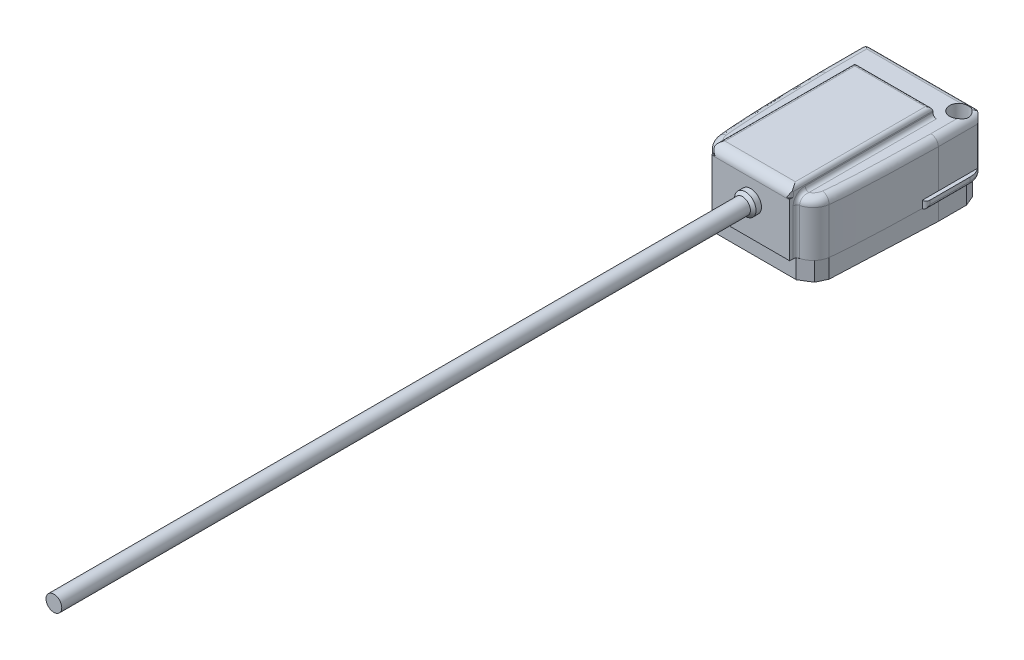
SolidWorks part; units mm, degrees
ref_plane "Front Plane" through (0, 0, 0) normal (0, 0, 1) x (1, 0, 0)
ref_plane "Top Plane" through (0, 0, 0) normal (0, 1, 0) x (1, 0, 0)
ref_plane "Right Plane" through (0, 0, 0) normal (1, 0, 0) x (0, 0, -1)
sketch "Sketch1" plane through (0, 0, 0) normal (0, 0, 1) x (1, 0, 0)
  circle A0 centre (0, 0) radius 4.2
  dimension "D1" = 8.4
extrude "Extrude1" add sketch "Sketch1" along normal blind 366.8
sketch "Sketch2" plane through (0, 0, 0) normal (0, 0, -1) x (-1, 0, 0)
  circle A0 centre (0, 0) radius 5.7
  dimension "D1" = 11.4
extrude "Extrude2" add sketch "Sketch2" along normal blind 4.4
chamfer "Chamfer1" distance 1.5 angle 45 1 edges at (-5.7, 0, 0)
sketch "Sketch3" plane through (0, 0, -4.4) normal (0, 0, -1) x (-1, 0, 0)
  line L1 (-34.1, 15.75) -> (34.1, 15.75)
  line L2 (-34.1, 15.75) -> (-34.1, -17.25)
  line L3 (-34.1, -17.25) -> (34.1, -17.25)
  line L4 (34.1, 15.75) -> (34.1, -17.25)
  circle A0 centre (0, 0) radius 5.7 construction
  dimension "D4" = 17.25
  dimension "D1" = 33
  dimension "D2" = 68.2
  dimension "D3" = 34.1
extrude "Extrude3" add sketch "Sketch3" along normal blind 92.8
sketch "Sketch4" plane through (-34.1, 0, 0) normal (-1, 0, 0) x (0, 0, 1)
  line L0 (-97.2, 15.75) -> (-4.4, 15.75) construction
  line L1 (-80.6, 41.999) -> (-107.8441, 41.999)
  line L2 (-80.6, 41.999) -> (-80.6, 11.15)
  line L3 (-80.6, 11.15) -> (-107.8441, 11.15)
  line L4 (-107.8441, 41.999) -> (-107.8441, 11.15)
  line L5 (-97.2, -17.25) -> (-97.2, 15.75) construction
  dimension "D1" = 4.6
  dimension "D2" = 16.6
extrude "Extrude4" cut sketch "Sketch4" against normal up to next
sketch "Sketch5" plane through (0, 0, -80.6) normal (0, 0, -1) x (-1, 0, 0)
  line L1 (20.75, 22.4945) -> (34.1, 22.4945)
  line L2 (20.75, 22.4945) -> (20.75, 11.15)
  line L3 (20.75, 11.15) -> (34.1, 11.15)
  line L4 (34.1, 22.4945) -> (34.1, 11.15)
  line L5 (-20.75, 22.4945) -> (-34.1, 22.4945)
  line L6 (-20.75, 22.4945) -> (-20.75, 11.15)
  line L7 (-20.75, 11.15) -> (-34.1, 11.15)
  line L8 (-34.1, 22.4945) -> (-34.1, 11.15)
  dimension "D1" = 41.5
  dimension "D2" = 13.35
  dimension "D3" = 13.35
extrude "Extrude5" cut sketch "Sketch5" against normal through all
sketch "Sketch6" plane through (0, 0, -97.2) normal (0, 0, -1) x (-1, 0, 0)
  line L0 (-34.1, -17.25) -> (34.1, -17.25) construction
  line L1 (32.1, 16.9028) -> (44.4445, 16.9028)
  line L2 (32.1, 16.9028) -> (32.1, -13.25)
  line L3 (32.1, -13.25) -> (44.4445, -13.25)
  line L4 (44.4445, 16.9028) -> (44.4445, -13.25)
  line L5 (-32.1, 22.2797) -> (-36.4812, 22.2797)
  line L6 (-32.1, 22.2797) -> (-32.1, -13.25)
  line L7 (-32.1, -13.25) -> (-36.4812, -13.25)
  line L8 (-36.4812, 22.2797) -> (-36.4812, -13.25)
  line L9 (-34.1, 11.15) -> (-34.1, -17.25) construction
  line L10 (34.1, -17.25) -> (34.1, 11.15) construction
  dimension "D1" = 4
  dimension "D2" = 4
  dimension "D3" = 2
  dimension "D4" = 2
extrude "Extrude6" cut sketch "Sketch6" against normal through all
sketch "Sketch7" plane through (0, -13.25, 0) normal (0, 1, 0) x (1, 0, 0)
  line L0 (32.1, 4.4) -> (32.1, 97.2) construction
  line L1 (58.6671, 1.609) -> (32.1, 1.609)
  line L2 (58.6671, 1.609) -> (58.6671, 63.7)
  line L3 (58.6671, 63.7) -> (32.1, 63.7)
  line L4 (32.1, 1.609) -> (32.1, 63.7)
  line L5 (-32.1, 4.4) -> (-32.1, 97.2) construction
  line L6 (-32.1, 63.7) -> (-46.2188, 63.7)
  line L7 (-32.1, 63.7) -> (-32.1, -25.5687)
  line L8 (-32.1, -25.5687) -> (-46.2188, -25.5687)
  line L9 (-46.2188, 63.7) -> (-46.2188, -25.5687)
  line L10 (-32.1, 97.2) -> (-34.1, 97.2) construction
  line L11 (34.1, 97.2) -> (32.1, 97.2) construction
  dimension "D1" = 33.5
  dimension "D2" = 33.5
extrude "Extrude7" cut sketch "Sketch7" against normal through all
fillet "Fillet2" radius 3 1 edges at (0, 11.15, -97.2)
fillet "Fillet3" radius 10 2 edges at (34.1, -15.25, -97.2) (-34.1, -15.25, -97.2)
fillet "Fillet20" radius 2 5 edges at (20.75, 13.45, -4.4) (20.75, 15.75, -42.5) (0, 15.75, -80.6) (-20.75, 15.75, -42.5) (-20.75, 13.45, -4.4)
fillet "Fillet7" radius 2 7 edges at (31.1711, -17.25, -94.2711) (-31.1711, -17.25, -94.2711) (-34.1, -15.25, -63.7) (34.1, -15.25, -63.7) (34.1, -17.25, -75.45) (0, -17.25, -97.2) (-34.1, -17.25, -75.45)
sketch "Sketch10" plane through (0, 15.75, 0) normal (0, 1, 0) x (1, 0, 0)
  line L0 (32.1, 4.4) -> (32.1, 93.2) construction
  line L2 (48.4518, 2.5489) -> (32.1, 35.6175)
  line L3 (-24.1, 97.2) -> (24.1, 97.2) construction
  line L4 (32.1, 35.6175) -> (32.1, 72.2)
  line L5 (48.4518, 2.5489) -> (34.583, 0.9729)
  line L6 (34.583, 0.9729) -> (26.1, 4.4)
  line L7 (-26.1, 4.4) -> (-37.3372, -2.8116)
  line L8 (-37.3372, -2.8116) -> (-32.1, 42.0539)
  line L9 (-32.1, 93.2) -> (-32.1, 4.4) construction
  line L10 (-32.1, 42.0539) -> (-32.1, 72.2)
  line L11 (18.75, 4.4) -> (18.75, 78.6) construction
  line L12 (-18.75, 4.4) -> (18.75, 4.4) construction
  spline S0 degree 3 poles (32.1, 72.2) (31.9027, 62.1371) (31.5864, 46.0005) (30.5599, 25.0431) (29.4595, 12.1255) (26.788, 5.9822) (26.1, 4.4) knots 0 0 0 0 0.440913 0.707031 0.924545 1 1 1 1
  spline S1 degree 3 poles (-32.1, 72.2) (-31.9027, 62.1371) (-31.5864, 46.0005) (-30.5599, 25.0431) (-29.4595, 12.1255) (-26.788, 5.9822) (-26.1, 4.4) knots 0 0 0 0 0.440913 0.707031 0.924545 1 1 1 1
  dimension "D1" = 25
  dimension "D2" = 6
extrude "Extrude10" cut sketch "Sketch10" against normal through all
sketch "Sketch11" plane through (0, 11.15, 0) normal (0, 1, 0) x (1, 0, 0)
  line L0 (20.75, 4.4) -> (20.75, 80.6) construction
  line L1 (20.75, 7.9) -> (51.0117, 7.9)
  line L2 (20.75, 7.9) -> (20.75, -9.7349)
  line L3 (20.75, -9.7349) -> (51.0117, -9.7349)
  line L4 (51.0117, 7.9) -> (51.0117, -9.7349)
  line L5 (-20.75, 6.4) -> (-20.75, 80.6) construction
  line L6 (-20.75, 7.9) -> (-46.0804, 7.9)
  line L7 (-20.75, 7.9) -> (-20.75, -17.0396)
  line L8 (-20.75, -17.0396) -> (-46.0804, -17.0396)
  line L9 (-46.0804, 7.9) -> (-46.0804, -17.0396)
  line L10 (-18.75, 4.4) -> (18.75, 4.4) construction
  dimension "D1" = 3.5
  dimension "D2" = 3.5
extrude "Extrude11" cut sketch "Sketch11" against normal through all
fillet "Fillet9" radius 10 2 edges at (27.5599, -3.05, -7.9) (-27.5599, -3.05, -7.9)
fillet "Fillet22" radius 4 6 edges at (26.6935, 11.15, -10.636) (32.1, 11.15, -82.7) (-32.1, 11.15, -82.7) (-26.6935, 11.15, -10.636)
fillet "Fillet13" radius 2 6 edges at (-20.75, -5.05, -7.9) (20.75, -5.05, -7.9) (20.75, 11.15, -46.2662) (20.75, 9.6387, -8.7731) (-20.75, 11.15, -46.2662) (-20.75, 10.1521, -9.2642)
sketch "Sketch14" plane through (20.75, 0, 0) normal (1, 0, 0) x (0, 0, -1)
  line L4 (9.4, 15.75) -> (9.4, 23.6066)
  line L5 (9.4, 23.6066) -> (-2.6621, 20.3015)
  line L6 (-2.6621, 20.3015) -> (2.008, 10.2427)
  line L7 (2.008, 10.2427) -> (4.4, 10.75)
  arc A0 (9.4, 15.75) -> (4.4, 10.75) centre (9.4, 10.75) ccw
  dimension "D3" = 10
extrude "Extrude12" cut sketch "Sketch14" against normal through all
sketch "Sketch15" plane through (0, 11.15, 0) normal (0, 1, 0) x (1, 0, 0)
  line L0 (-24.1, 97.2) -> (24.1, 97.2) construction
  line L1 (32.1, 72.2) -> (32.1, 93.2) construction
  circle A0 centre (25.1, 90.2) radius 5
  dimension "D1" = 10
  dimension "D2" = 7
  dimension "D3" = 7
extrude "Extrude13" cut sketch "Sketch15" against normal blind 10
sketch "Sketch16" plane through (0, 1.15, 0) normal (0, 1, 0) x (1, 0, 0)
  circle A0 centre (25.1, 90.2) radius 2.5
  dimension "D1" = 5
extrude "Extrude14" cut sketch "Sketch16" against normal blind 10
sketch "Sketch17" plane through (0, -17.25, 0) normal (0, -1, 0) x (1, 0, 0)
  line L0 (24.1, -97.2) -> (-24.1, -97.2) construction
  line L1 (32.1, -87.2) -> (32.1, -72.2) construction
  line L2 (-32.1, -72.2) -> (-32.1, -87.2) construction
  line L4 (-19.9, -35.4) -> (-11.9, -35.4)
  line L5 (-19.9, -35.4) -> (-19.9, -43.4)
  line L6 (-19.9, -43.4) -> (-11.9, -43.4)
  line L7 (-11.9, -35.4) -> (-11.9, -43.4)
  line L8 (11.9, -35.4) -> (19.9, -35.4)
  line L9 (11.9, -35.4) -> (11.9, -43.4)
  line L10 (11.9, -43.4) -> (19.9, -43.4)
  line L11 (19.9, -35.4) -> (19.9, -43.4)
  line L12 (11.9, -67.2) -> (19.9, -67.2)
  line L13 (11.9, -67.2) -> (11.9, -75.2)
  line L14 (11.9, -75.2) -> (19.9, -75.2)
  line L15 (19.9, -67.2) -> (19.9, -75.2)
  line L16 (-19.9, -67.2) -> (-11.9, -67.2)
  line L17 (-19.9, -67.2) -> (-19.9, -75.2)
  line L18 (-19.9, -75.2) -> (-11.9, -75.2)
  line L19 (-11.9, -67.2) -> (-11.9, -75.2)
  circle A0 centre (-15.9, -39.4) radius 7.5
  circle A1 centre (15.9, -39.4) radius 7.5
  circle A2 centre (-15.9, -71.2) radius 7.5
  circle A3 centre (15.9, -71.2) radius 7.5
  dimension "D1" = 15
  dimension "D2" = 15
  dimension "D3" = 15
  dimension "D4" = 15
  dimension "D26" = 8
  dimension "D5" = 31.8
  dimension "D6" = 31.8
  dimension "D7" = 26
  dimension "D8" = 26
  dimension "D9" = 16.2
  dimension "D10" = 31.8
  dimension "D11" = 31.8
  dimension "D12" = 16.2
  dimension "D13" = 16.2
  dimension "D14" = 4
  dimension "D15" = 4
  dimension "D16" = 4
  dimension "D17" = 4
  dimension "D18" = 8
  dimension "D19" = 8
  dimension "D20" = 4
  dimension "D21" = 4
  dimension "D22" = 8
  dimension "D23" = 8
  dimension "D24" = 4
  dimension "D25" = 4
  dimension "D27" = 8
  dimension "D28" = 4
  dimension "D29" = 4
extrude "Extrude15" cut sketch "Sketch17" against normal blind 3
sketch "Sketch18" plane through (0, -17.25, 0) normal (0, -1, 0) x (1, 0, 0)
  line L0 (-27.224, -11.1854) -> (-21.1699, -7.4538)
  line L1 (-27.224, -11.1854) -> (-29.6731, -16.4611)
  line L2 (-29.6731, -16.4611) -> (-32.1, -72.2)
  line L3 (-32.1, -72.2) -> (-32.1, -87.2)
  line L4 (-32.1, -87.2) -> (-29.7569, -92.8569)
  line L5 (-29.7569, -92.8569) -> (-24.1, -95.2)
  line L6 (-24.1, -95.2) -> (24.1, -95.2)
  line L7 (24.1, -95.2) -> (29.7569, -92.8569)
  line L8 (29.7569, -92.8569) -> (32.1, -87.2)
  line L9 (32.1, -87.2) -> (32.1, -72.2)
  line L10 (32.1, -72.2) -> (29.6731, -16.4611)
  line L11 (29.6731, -16.4611) -> (27.224, -11.1854)
  line L12 (27.224, -11.1854) -> (21.1699, -7.4538)
  line L13 (21.1699, -7.4538) -> (-21.1699, -7.4538)
  arc A0 (-22.2534, -8.1651) -> (-20.75, -6.2277) centre (-22.75, -6.2277) ccw construction
  arc A1 (-22.2534, -8.1651) -> (-29.6731, -16.4611) centre (-19.7703, -17.8519) ccw construction
  arc A2 (-32.1, -87.2) -> (-24.1, -95.2) centre (-24.1, -87.2) ccw construction
  arc A3 (24.1, -95.2) -> (32.1, -87.2) centre (24.1, -87.2) ccw construction
  arc A4 (29.6731, -16.4611) -> (22.2534, -8.1651) centre (19.7703, -17.8519) ccw construction
  arc A5 (20.75, -6.2277) -> (22.2534, -8.1651) centre (22.75, -6.2277) ccw construction
  circle A6 centre (-15.9, -39.4) radius 7.5
  circle A7 centre (15.9, -39.4) radius 7.5
  circle A8 centre (15.9, -71.2) radius 7.5
  circle A9 centre (-15.9, -71.2) radius 7.5
extrude "Extrude16" add sketch "Sketch18" along normal blind 10.05
sketch "Sketch19" plane through (0, -17.25, 0) normal (0, -1, 0) x (1, 0, 0)
  line L1 (-19.9, -35.4) -> (-11.9, -35.4)
  line L2 (-19.9, -35.4) -> (-19.9, -43.4)
  line L3 (-19.9, -43.4) -> (-11.9, -43.4)
  line L4 (-11.9, -35.4) -> (-11.9, -43.4)
  line L5 (11.9, -35.4) -> (19.9, -35.4)
  line L6 (11.9, -35.4) -> (11.9, -43.4)
  line L7 (11.9, -43.4) -> (19.9, -43.4)
  line L8 (19.9, -35.4) -> (19.9, -43.4)
  line L9 (11.9, -67.2) -> (19.9, -67.2)
  line L10 (11.9, -67.2) -> (11.9, -75.2)
  line L11 (11.9, -75.2) -> (19.9, -75.2)
  line L12 (19.9, -67.2) -> (19.9, -75.2)
  line L13 (-19.9, -67.2) -> (-11.9, -67.2)
  line L14 (-19.9, -67.2) -> (-19.9, -75.2)
  line L15 (-19.9, -75.2) -> (-11.9, -75.2)
  line L16 (-11.9, -67.2) -> (-11.9, -75.2)
extrude "Extrude17" add sketch "Sketch19" along normal blind 10.05
